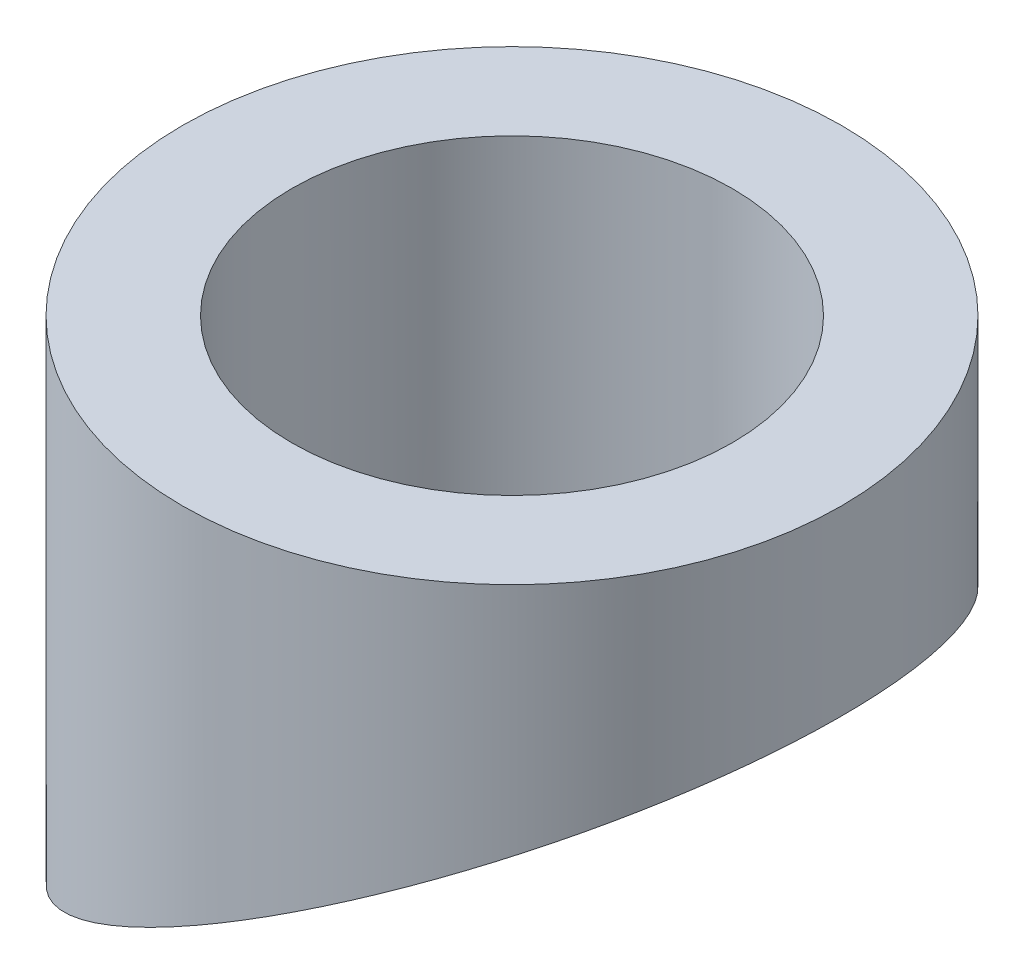
SolidWorks part; units mm, degrees
ref_plane "Front Plane" through (0, 0, 0) normal (0, 0, 1) x (1, 0, 0)
ref_plane "Top Plane" through (0, 0, 0) normal (0, 1, 0) x (1, 0, 0)
ref_plane "Right Plane" through (0, 0, 0) normal (1, 0, 0) x (0, 0, -1)
sketch "Sketch1" plane through (0, 0, 0) normal (0, 1, 0) x (1, 0, 0)
  circle A0 centre (0, 0) radius 6.05
  circle A1 centre (0, 0) radius 9.05
  dimension "D1" = 12.1
  dimension "D2" = 3
extrude "Boss-Extrude1" add sketch "Sketch1" along normal blind 15
sketch "Sketch3" plane through (0, 0, 0) normal (0, 0, 1) x (1, 0, 0)
  line L0 (-9.05, 0) -> (9.05, 10)
  line L1 (9.05, 0) -> (9.05, 15) construction
  line L2 (9.05, 10) -> (9.05, 0)
  line L3 (9.05, 0) -> (-9.05, 0)
  dimension "D1" = 10
extrude "Cut-Extrude1" cut sketch "Sketch3" against normal mid plane 30
